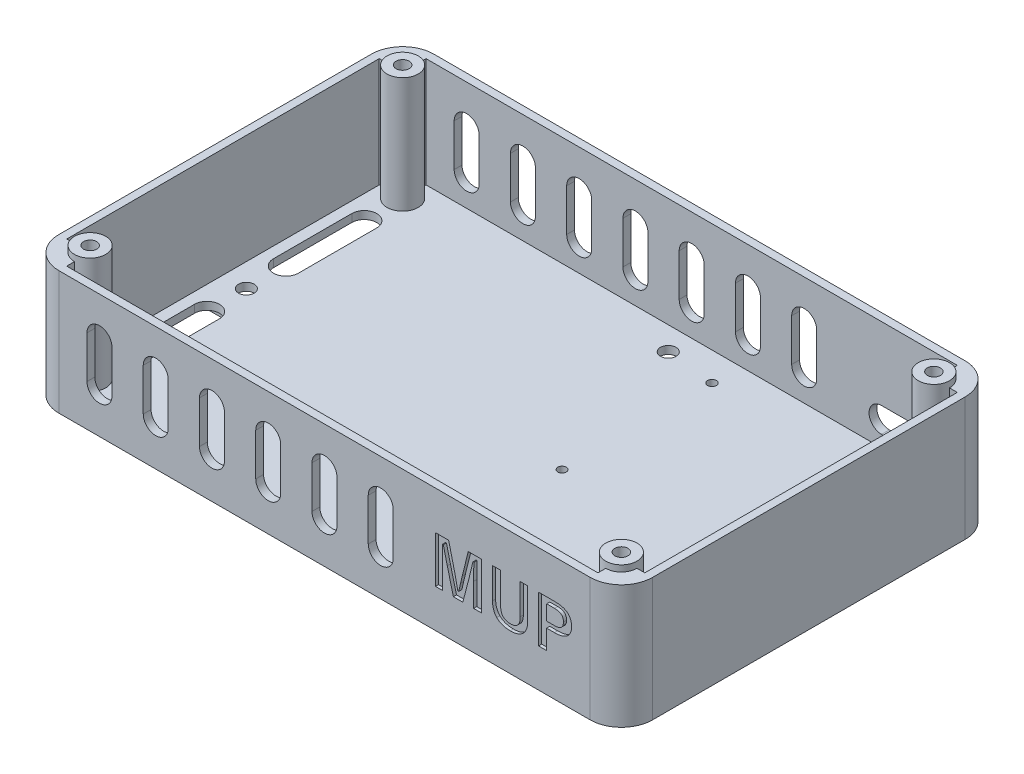
SolidWorks part; units mm, degrees
ref_plane "Front Plane" through (0, 0, 0) normal (0, 0, 1) x (1, 0, 0)
ref_plane "Top Plane" through (0, 0, 0) normal (0, 1, 0) x (1, 0, 0)
ref_plane "Right Plane" through (0, 0, 0) normal (1, 0, 0) x (0, 0, -1)
sketch "Sketch1" plane through (0, 94.5, 0) normal (0, 1, 0) x (1, 0, 0)
  line L0 (7.3241, -194.8914) -> (7.3241, -202.3914)
  line L1 (-7.6759, -194.8914) -> (-7.6759, -202.3914)
  line L2 (-85.1759, -152.3914) -> (-92.6759, -152.3914)
  line L3 (-84.9375, -137.4848) -> (-92.6759, -137.4848)
  line L4 (7.3241, -94.8914) -> (7.3241, -87.3914)
  line L5 (-7.6415, -94.1735) -> (-7.6759, -94.1891)
  line L7 (-7.6759, -94.8914) -> (-7.6759, -87.3914)
  line L9 (84.8241, -152.3914) -> (92.3241, -152.3914)
  line L10 (84.8241, -137.3914) -> (92.3241, -137.3914)
  line L16 (84.8241, -87.3914) -> (4.8241, -87.3914)
  line L17 (4.8241, -87.3914) -> (4.8241, -94.8914)
  line L18 (-5.1759, -94.8914) -> (-5.1759, -87.3914)
  line L19 (-5.1759, -87.3914) -> (-85.1759, -87.3914)
  line L20 (-92.6759, -94.8914) -> (-92.6759, -139.8914)
  line L21 (-92.6759, -139.8914) -> (-85.1759, -139.8914)
  line L22 (-85.1759, -149.8914) -> (-92.6759, -149.8914)
  line L23 (-92.6759, -149.8914) -> (-92.6759, -194.8914)
  line L24 (-85.1759, -202.3914) -> (-5.1759, -202.3914)
  line L25 (-5.1759, -202.3914) -> (-5.1759, -194.8914)
  line L26 (4.8241, -194.8914) -> (4.8241, -202.3914)
  line L27 (4.8241, -202.3914) -> (84.8241, -202.3914)
  line L28 (92.3241, -194.8914) -> (92.3241, -149.8914)
  line L29 (92.3241, -149.8914) -> (84.8241, -149.8914)
  line L30 (84.8241, -139.8914) -> (92.3241, -139.8914)
  line L31 (92.3241, -139.8914) -> (92.3241, -94.8914)
  line L32 (84.8241, -87.3914) -> (7.3241, -87.3914)
  line L35 (-7.6759, -87.3914) -> (-85.1759, -87.3914)
  line L36 (-92.6759, -94.8914) -> (-92.6759, -137.4848)
  line L39 (-92.6759, -152.3914) -> (-92.6759, -194.8914)
  line L40 (-85.1759, -202.3914) -> (-7.6759, -202.3914)
  line L43 (7.3241, -202.3914) -> (84.8241, -202.3914)
  line L44 (92.3241, -194.8914) -> (92.3241, -152.3914)
  line L47 (92.3241, -137.3914) -> (92.3241, -94.8914)
  circle A0 centre (84.8241, -144.8914) radius 5.5
  circle A1 centre (-0.1759, -194.8914) radius 5.5
  circle A2 centre (-85.1759, -144.8914) radius 5.5
  circle A3 centre (-0.1759, -94.8914) radius 5.5
  circle A5 centre (-0.1759, -194.8914) radius 7.5
  circle A7 centre (-0.1759, -94.8914) radius 7.5
  arc A8 (92.3241, -94.8914) -> (84.8241, -87.3914) centre (84.8241, -94.8914) ccw
  arc A9 (-5.1759, -94.8914) -> (4.8241, -94.8914) centre (-0.1759, -94.8914) ccw
  arc A10 (-85.1759, -87.3914) -> (-92.6759, -94.8914) centre (-85.1759, -94.8914) ccw
  arc A11 (-85.1759, -149.8914) -> (-85.1759, -139.8914) centre (-85.1759, -144.8914) ccw
  arc A12 (-92.6759, -194.8914) -> (-85.1759, -202.3914) centre (-85.1759, -194.8914) ccw
  arc A13 (4.8241, -194.8914) -> (-5.1759, -194.8914) centre (-0.1759, -194.8914) ccw
  arc A14 (84.8241, -202.3914) -> (92.3241, -194.8914) centre (84.8241, -194.8914) ccw
  arc A15 (84.8241, -139.8914) -> (84.8241, -149.8914) centre (84.8241, -144.8914) ccw
  arc A16 (92.3241, -94.8914) -> (84.8241, -87.3914) centre (84.8241, -94.8914) ccw
  arc A18 (-85.1759, -87.3914) -> (-92.6759, -94.8914) centre (-85.1759, -94.8914) ccw
  arc A20 (-92.6759, -194.8914) -> (-85.1759, -202.3914) centre (-85.1759, -194.8914) ccw
  arc A22 (84.8241, -202.3914) -> (92.3241, -194.8914) centre (84.8241, -194.8914) ccw
  circle A24 centre (84.8241, -144.8914) radius 7.5
  circle A25 centre (-85.1759, -144.8914) radius 7.5
  arc A26 (-88.9375, -133.4848) -> (-80.9375, -133.4848) centre (-84.9375, -133.4848) ccw construction
  line M25 (84.8241, -84.8914) -> (-85.1759, -84.8914)
  arc M26 (-85.1759, -84.8914) -> (-95.1759, -94.8914) centre (-85.1759, -94.8914) ccw
  line M27 (-95.1759, -94.8914) -> (-95.1759, -194.8914)
  arc M28 (-95.1759, -194.8914) -> (-85.1759, -204.8914) centre (-85.1759, -194.8914) ccw
  line M29 (-85.1759, -204.8914) -> (84.8241, -204.8914)
  arc M30 (84.8241, -204.8914) -> (94.8241, -194.8914) centre (84.8241, -194.8914) ccw
  line M31 (94.8241, -194.8914) -> (94.8241, -94.8914)
  arc M32 (94.8241, -94.8914) -> (84.8241, -84.8914) centre (84.8241, -94.8914) ccw
  line M33 (4.8241, -202.3914) -> (4.8241, -194.8914)
  line M35 (-5.1759, -194.8914) -> (-5.1759, -202.3914)
  line M36 (-5.1759, -202.3914) -> (-85.1759, -202.3914)
  arc M37 (-85.1759, -202.3914) -> (-92.6759, -194.8914) centre (-85.1759, -194.8914) cw
  line M38 (-92.6759, -194.8914) -> (-92.6759, -149.8914)
  line M39 (-92.6759, -149.8914) -> (-85.1759, -149.8914)
  line M41 (-85.1759, -139.8914) -> (-92.6759, -139.8914)
  line M42 (-92.6759, -139.8914) -> (-92.6759, -94.8914)
  arc M43 (-92.6759, -94.8914) -> (-85.1759, -87.3914) centre (-85.1759, -94.8914) cw
  line M44 (-85.1759, -87.3914) -> (-5.1759, -87.3914)
  line M45 (-5.1759, -87.3914) -> (-5.1759, -94.8914)
  line M47 (4.8241, -94.8914) -> (4.8241, -87.3914)
  line M48 (4.8241, -87.3914) -> (84.8241, -87.3914)
  arc M49 (84.8241, -87.3914) -> (92.3241, -94.8914) centre (84.8241, -94.8914) cw
  line M50 (92.3241, -94.8914) -> (92.3241, -139.8914)
  line M51 (92.3241, -139.8914) -> (84.8241, -139.8914)
  line M53 (84.8241, -149.8914) -> (92.3241, -149.8914)
  line M54 (92.3241, -149.8914) -> (92.3241, -194.8914)
  arc M55 (92.3241, -194.8914) -> (84.8241, -202.3914) centre (84.8241, -194.8914) cw
  line M56 (84.8241, -202.3914) -> (4.8241, -202.3914)
  dimension "D2" = 11
  dimension "D1" = 0
extrude "Boss-Extrude1" add sketch "Sketch1" along normal blind 2 contours A25 A7 A24 A5 M32 M25 M26 M27 M28 M29 M30 M31 M41 M42 M43 M44 M45 M47 M48 M49 M50 M51 M53 M54 M55 M56 M33 M35 M36 M37 M38 M39 | A24 A0 M53 M51 | A24 A0 M53 M51 | A24 L9 M54 M53 | A24 L10 M51 M50 | A5 A1 M33 M35 | A5 A1 M35 M33 | A5 L0 M33 M56 | A5 L1 M36 M35 | A25 L2 M39 M38 | A25 L3 M42 M41 | A25 A2 M41 M39 | A25 A2 M41 M39 | A7 A3 M47 M45 | A7 A3 M47 M45 | A7 L4 M48 M47 | A7 L7 L5 M45 M44 region at (6.4889, 94.5, 197.872) region at (6.324, 94.5, 200.3464) region at (-6.6758, 94.5, 200.3464) region at (-0.1759, 94.5, 200.5378) region at (90.2791, 94.5, 151.3913) region at (77.5231, 94.5, 144.8914) region at (-90.631, 94.5, 151.3913) region at (90.2791, 94.5, 138.3915) region at (90.4705, 94.5, 144.8914) region at (-88.1565, 94.5, 151.5562) region at (-90.8224, 94.5, 144.8914) region at (-90.7288, 94.5, 138.4624) region at (6.324, 94.5, 89.4364) region at (-0.1759, 94.5, 102.1923) region at (-0.1759, 94.5, 89.245) region at (-6.675, 94.5, 89.432) region at (90.3061, 94.5, 89.4094)
sketch "Sketch2" plane through (0, 96.5, 0) normal (0, 1, 0) x (1, 0, 0)
  line L4 (84.8241, -84.8914) -> (-85.1759, -84.8914)
  line L5 (-95.1759, -94.8914) -> (-95.1759, -194.8914)
  line L6 (-85.1759, -204.8914) -> (84.8241, -204.8914)
  line L7 (94.8241, -194.8914) -> (94.8241, -94.8914)
  line L8 (84.8241, -84.8914) -> (-85.1759, -84.8914)
  line L9 (-95.1759, -94.8914) -> (-95.1759, -194.8914)
  line L10 (-85.1759, -204.8914) -> (84.8241, -204.8914)
  line L11 (94.8241, -194.8914) -> (94.8241, -94.8914)
  arc A4 (94.8241, -94.8914) -> (84.8241, -84.8914) centre (84.8241, -94.8914) ccw
  arc A5 (-85.1759, -84.8914) -> (-95.1759, -94.8914) centre (-85.1759, -94.8914) ccw
  arc A6 (-95.1759, -194.8914) -> (-85.1759, -204.8914) centre (-85.1759, -194.8914) ccw
  arc A7 (84.8241, -204.8914) -> (94.8241, -194.8914) centre (84.8241, -194.8914) ccw
  arc A8 (94.8241, -94.8914) -> (84.8241, -84.8914) centre (84.8241, -94.8914) ccw
  arc A9 (-85.1759, -84.8914) -> (-95.1759, -94.8914) centre (-85.1759, -94.8914) ccw
  arc A10 (-95.1759, -194.8914) -> (-85.1759, -204.8914) centre (-85.1759, -194.8914) ccw
  arc A11 (84.8241, -204.8914) -> (94.8241, -194.8914) centre (84.8241, -194.8914) ccw
  dimension "D1" = 0
extrude "Boss-Extrude2" add sketch "Sketch2" along normal blind 2.5
sketch "Sketch5" plane through (0, 99, 0) normal (0, 1, 0) x (1, 0, 0)
  line L4 (-95.1759, -144.8914) -> (108.7771, -144.8914) construction
  line L5 (-95.1759, -94.8914) -> (-95.1759, -194.8914) construction
  line L8 (-80.9375, -132.4549) -> (-80.9375, -107.3914)
  line L9 (-88.9375, -107.3914) -> (-88.9375, -132.4549)
  line L10 (-88.9375, -182.3914) -> (-88.9375, -157.3279)
  line L11 (-80.9375, -157.3279) -> (-80.9375, -182.3914)
  line L16 (-85.1759, -89.8914) -> (-85.1759, -87.3914)
  line L17 (-90.1759, -94.8914) -> (-92.6759, -94.8914)
  line L18 (-92.6759, -194.8914) -> (-90.1759, -194.8914)
  line L19 (-85.1759, -199.8914) -> (-85.1759, -202.3914)
  line L20 (84.8241, -87.3914) -> (-85.1759, -87.3914)
  line L21 (-92.6759, -94.8914) -> (-92.6759, -194.8914)
  line L22 (-85.1759, -202.3914) -> (84.8241, -202.3914)
  line L23 (92.3241, -194.8914) -> (92.3241, -94.8914)
  line L24 (84.8241, -87.3914) -> (-85.1759, -87.3914)
  line L25 (-92.6759, -94.8914) -> (-92.6759, -194.8914)
  line L26 (-85.1759, -202.3914) -> (84.8241, -202.3914)
  line L27 (92.3241, -194.8914) -> (92.3241, -94.8914)
  line L28 (84.8241, -87.3914) -> (84.8241, -89.8914)
  line L29 (92.3241, -94.8914) -> (89.8241, -94.8914)
  line L30 (84.8241, -199.8914) -> (84.8241, -202.3914)
  line L31 (92.3241, -194.8914) -> (89.8241, -194.8914)
  circle A0 centre (-85.1759, -94.8914) radius 5
  circle A1 centre (84.8241, -94.8914) radius 5
  circle A2 centre (84.8241, -194.8914) radius 5
  circle A3 centre (-85.1759, -194.8914) radius 5
  arc A8 (-88.9375, -157.3279) -> (-80.9375, -157.3279) centre (-84.9375, -157.3279) cw
  arc A9 (-80.9375, -182.3914) -> (-88.9375, -182.3914) centre (-84.9375, -182.3914) cw
  arc A12 (-88.9375, -132.4549) -> (-80.9375, -132.4549) centre (-84.9375, -132.4549) ccw
  arc A13 (-80.9375, -107.3914) -> (-88.9375, -107.3914) centre (-84.9375, -107.3914) ccw
  arc A22 (92.3241, -94.8914) -> (84.8241, -87.3914) centre (84.8241, -94.8914) ccw
  arc A23 (-85.1759, -87.3914) -> (-92.6759, -94.8914) centre (-85.1759, -94.8914) ccw
  arc A24 (-92.6759, -194.8914) -> (-85.1759, -202.3914) centre (-85.1759, -194.8914) ccw
  arc A25 (84.8241, -202.3914) -> (92.3241, -194.8914) centre (84.8241, -194.8914) ccw
  arc A26 (92.3241, -94.8914) -> (84.8241, -87.3914) centre (84.8241, -94.8914) ccw
  arc A27 (-85.1759, -87.3914) -> (-92.6759, -94.8914) centre (-85.1759, -94.8914) ccw
  arc A28 (-92.6759, -194.8914) -> (-85.1759, -202.3914) centre (-85.1759, -194.8914) ccw
  arc A29 (84.8241, -202.3914) -> (92.3241, -194.8914) centre (84.8241, -194.8914) ccw
  point P14 (-84.9375, -103.3914)
  arc M14 (94.8241, -94.8914) -> (84.8241, -84.8914) centre (84.8241, -94.8914) ccw
  line M15 (84.8241, -84.8914) -> (-85.1759, -84.8914)
  arc M16 (-85.1759, -84.8914) -> (-95.1759, -94.8914) centre (-85.1759, -94.8914) ccw
  line M17 (-95.1759, -94.8914) -> (-95.1759, -194.8914)
  arc M18 (-95.1759, -194.8914) -> (-85.1759, -204.8914) centre (-85.1759, -194.8914) ccw
  line M19 (-85.1759, -204.8914) -> (84.8241, -204.8914)
  arc M20 (84.8241, -204.8914) -> (94.8241, -194.8914) centre (84.8241, -194.8914) ccw
  line M21 (94.8241, -194.8914) -> (94.8241, -94.8914)
  dimension "D1" = 18.5
  dimension "D2" = 2.5
extrude "Boss-Extrude4" add sketch "Sketch5" along normal blind 35 contours L4 L25 A27 L24 A26 L27 M17 M21 M14 M15 M16 | L4 L27 A29 L26 A28 L25 M17 M18 M19 M20 M21 | L16 A27 L17 A0 | A0 | A3 | L18 A28 L19 A3 | A2 | L30 A29 L31 A2 | A1 | L29 A26 L28 A1 region at (-93.1835, 99, 119.8914) region at (-93.9259, 99, 146.8839) region at (-89.2079, 99, 90.8595) region at (-89.2079, 99, 198.9233) region at (88.856, 99, 198.9233) region at (88.856, 99, 90.8595) region at (-85.1759, 99, 94.8914) region at (-85.1759, 99, 194.8914) region at (84.8241, 99, 194.8914) region at (84.8241, 99, 94.8914)
hole_wizard "Ø5.0 (5) Diameter Hole1" positions "Sketch6" profile "Sketch7" hole size "Ø5.0" standard "ISO"
sketch "Sketch6" plane through (0, 99, 0) normal (0, 1, 0) x (1, 0, 0)
  point P0 (-0.1759, -94.8914)
  point P3 (-85.1759, -144.8914)
  point P6 (84.8241, -144.8914)
  point P9 (-0.1759, -194.8914)
sketch "Sketch7" plane through (-0.1759, 99, 94.8914) normal (1, 0, 0) x (0, 0, 1)
  line L0 (0, 0) -> (0, 4.0022)
  line L1 (0, 4.0022) -> (2.5, 2.5)
  line L2 (2.5, 2.5) -> (2.5, 0)
  line L5 (2.5, 0) -> (0, 0)
  line L10 (0, 4.0022) -> (-2.5, 2.5) construction
  line L11 (0, -6.35) -> (0, 107.95) construction
  dimension "Hole Dia." = 5
  dimension "Hole Depth" = 2.5
  dimension "Drill Angle" = 118
sketch "Sketch8" plane through (0, 134, 0) normal (0, 1, 0) x (1, 0, 0)
  circle A0 centre (-85.1759, -194.8914) radius 5
  circle A1 centre (-85.1759, -94.8914) radius 5
  circle A2 centre (84.8241, -94.8914) radius 5
  circle A3 centre (84.8241, -194.8914) radius 5
extrude "Boss-Extrude5" add sketch "Sketch8" along normal blind 2
hole_wizard "Tap Drill for M5 Tap1" positions "Sketch9" profile "Sketch10" hole size "M5" standard "ISO"
sketch "Sketch9" plane through (0, 136, 0) normal (0, 1, 0) x (1, 0, 0)
  point P0 (-85.1759, -94.8914)
  point P3 (-85.1759, -194.8914)
  point P6 (84.8241, -94.8914)
  point P9 (84.8241, -194.8914)
sketch "Sketch10" plane through (-85.1759, 136, 94.8914) normal (1, 0, 0) x (0, 0, 1)
  line L0 (0, 0) -> (0, 21.2618)
  line L1 (0, 21.2618) -> (2.1, 20)
  line L2 (2.1, 20) -> (2.1, 0)
  line L5 (2.1, 0) -> (0, 0)
  line L10 (0, 21.2618) -> (-2.1, 20) construction
  line L11 (0, -6.35) -> (0, 107.95) construction
  dimension "Hole Dia." = 4.2
  dimension "Hole Depth" = 20
  dimension "Drill Angle" = 118
sketch "Sketch11" plane through (0, 99, 0) normal (0, 1, 0) x (1, 0, 0)
  line L2 (-92.6759, -144.8914) -> (-43.1546, -144.8914) construction
  line L3 (-92.6759, -94.8914) -> (-92.6759, -194.8914) construction
  line L6 (-81.1408, -132.2653) -> (-81.1408, -107.2017)
  line L7 (-89.1408, -107.2017) -> (-89.1408, -132.2653)
  line L8 (-89.1408, -182.5811) -> (-89.1408, -157.5175)
  line L9 (-81.1408, -157.5175) -> (-81.1408, -182.5811)
  arc A2 (-81.1408, -182.5811) -> (-89.1408, -182.5811) centre (-85.1408, -182.5811) cw
  arc A3 (-89.1408, -157.5175) -> (-81.1408, -157.5175) centre (-85.1408, -157.5175) cw
  arc A6 (-89.1408, -132.2653) -> (-81.1408, -132.2653) centre (-85.1408, -132.2653) ccw
  arc A7 (-81.1408, -107.2017) -> (-89.1408, -107.2017) centre (-85.1408, -107.2017) ccw
extrude "Cut-Extrude2" cut sketch "Sketch11" against normal blind 2.5
sketch "Sketch12" plane through (0, 99, 0) normal (0, 1, 0) x (1, 0, 0)
  circle A4 centre (19.3504, -155.4853) radius 1.1
  circle A5 centre (77.3504, -155.4853) radius 1.1
  circle A6 centre (77.3504, -113.9352) radius 1.1
  circle A7 centre (19.3504, -113.9352) radius 1.1
sketch "Sketch16" plane through (0, 99, 0) normal (0, 1, 0) x (1, 0, 0)
  line L0 (92.3241, -194.8914) -> (92.3241, -94.8914) construction
  line L1 (74.7241, -101.3914) -> (16.7241, -101.3914) construction
  line L2 (74.7241, -101.3914) -> (74.7241, -149.3914) construction
  line L3 (74.7241, -149.3914) -> (16.7241, -149.3914) construction
  line L4 (16.7241, -101.3914) -> (16.7241, -149.3914) construction
  line L5 (84.8241, -87.3914) -> (-85.1759, -87.3914) construction
  dimension "D1" = 48
  dimension "D2" = 58
  dimension "D3" = 17.6
  dimension "D4" = 14
sketch "Sketch17" plane through (0, 99, 0) normal (0, 1, 0) x (1, 0, 0)
  circle A0 centre (15.4697, -144.5267) radius 1.35
  circle A1 centre (15.4697, -96.5267) radius 1.4045
  circle A2 centre (73.4697, -144.5267) radius 1.35
  circle A3 centre (73.4697, -96.5267) radius 1.35
extrude "Cut-Extrude3" cut sketch "Sketch17" against normal blind 2.5
sketch "Sketch18" plane through (0, 0, 204.8914) normal (0, 0, 1) x (1, 0, 0)
  line L2 (-74.4259, 117.75) -> (-60.9259, 117.75)
  line L3 (-60.9259, 125.75) -> (-74.4259, 125.75)
  line L4 (-85.1759, 134) -> (84.8241, 134) construction
  line L5 (-33.9259, 125.75) -> (-47.4259, 125.75)
  line L6 (-47.4259, 117.75) -> (-33.9259, 117.75)
  line L7 (-6.9259, 125.75) -> (-20.4259, 125.75)
  line L8 (-20.4259, 117.75) -> (-6.9259, 117.75)
  line L9 (20.0741, 125.75) -> (6.5741, 125.75)
  line L10 (6.5741, 117.75) -> (20.0741, 117.75)
  line L15 (-33.9259, 110.75) -> (-47.4259, 110.75)
  line L16 (-47.4259, 102.75) -> (-33.9259, 102.75)
  line L17 (-6.9259, 110.75) -> (-20.4259, 110.75)
  line L18 (-20.4259, 102.75) -> (-6.9259, 102.75)
  line L19 (20.0741, 110.75) -> (6.5741, 110.75)
  line L20 (6.5741, 102.75) -> (20.0741, 102.75)
  line L25 (-60.9259, 110.75) -> (-74.4259, 110.75)
  line L26 (-74.4259, 102.75) -> (-60.9259, 102.75)
  line L27 (-60.9259, 125.75) -> (-33.9259, 125.75) construction
  line L28 (-60.9259, 125.75) -> (-60.9259, 110.75) construction
  line L30 (47.0741, 125.75) -> (33.5741, 125.75) [skipped]
  line L31 (33.5741, 117.75) -> (47.0741, 117.75) [skipped]
  line L32 (74.0741, 125.75) -> (60.5741, 125.75) [skipped]
  line L33 (60.5741, 117.75) -> (74.0741, 117.75) [skipped]
  line L34 (47.0741, 110.75) -> (33.5741, 110.75) [skipped]
  line L35 (33.5741, 102.75) -> (47.0741, 102.75) [skipped]
  line L36 (74.0741, 110.75) -> (60.5741, 110.75) [skipped]
  line L37 (60.5741, 102.75) -> (74.0741, 102.75) [skipped]
  arc A2 (-60.9259, 117.75) -> (-60.9259, 125.75) centre (-60.9259, 121.75) ccw
  arc A3 (-74.4259, 125.75) -> (-74.4259, 117.75) centre (-74.4259, 121.75) ccw
  arc A4 (-33.9259, 117.75) -> (-33.9259, 125.75) centre (-33.9259, 121.75) ccw
  arc A5 (-47.4259, 125.75) -> (-47.4259, 117.75) centre (-47.4259, 121.75) ccw
  arc A6 (-6.9259, 117.75) -> (-6.9259, 125.75) centre (-6.9259, 121.75) ccw
  arc A7 (-20.4259, 125.75) -> (-20.4259, 117.75) centre (-20.4259, 121.75) ccw
  arc A8 (20.0741, 117.75) -> (20.0741, 125.75) centre (20.0741, 121.75) ccw
  arc A9 (6.5741, 125.75) -> (6.5741, 117.75) centre (6.5741, 121.75) ccw
  arc A14 (-33.9259, 102.75) -> (-33.9259, 110.75) centre (-33.9259, 106.75) ccw
  arc A15 (-47.4259, 110.75) -> (-47.4259, 102.75) centre (-47.4259, 106.75) ccw
  arc A16 (-6.9259, 102.75) -> (-6.9259, 110.75) centre (-6.9259, 106.75) ccw
  arc A17 (-20.4259, 110.75) -> (-20.4259, 102.75) centre (-20.4259, 106.75) ccw
  arc A18 (20.0741, 102.75) -> (20.0741, 110.75) centre (20.0741, 106.75) ccw
  arc A19 (6.5741, 110.75) -> (6.5741, 102.75) centre (6.5741, 106.75) ccw
  arc A24 (-60.9259, 102.75) -> (-60.9259, 110.75) centre (-60.9259, 106.75) ccw
  arc A25 (-74.4259, 110.75) -> (-74.4259, 102.75) centre (-74.4259, 106.75) ccw
  arc A26 (47.0741, 117.75) -> (47.0741, 125.75) centre (47.0741, 121.75) ccw [skipped]
  arc A27 (33.5741, 125.75) -> (33.5741, 117.75) centre (33.5741, 121.75) ccw [skipped]
  arc A28 (74.0741, 117.75) -> (74.0741, 125.75) centre (74.0741, 121.75) ccw [skipped]
  arc A29 (60.5741, 125.75) -> (60.5741, 117.75) centre (60.5741, 121.75) ccw [skipped]
  arc A30 (47.0741, 102.75) -> (47.0741, 110.75) centre (47.0741, 106.75) ccw [skipped]
  arc A31 (33.5741, 110.75) -> (33.5741, 102.75) centre (33.5741, 106.75) ccw [skipped]
  arc A32 (74.0741, 102.75) -> (74.0741, 110.75) centre (74.0741, 106.75) ccw [skipped]
  arc A33 (60.5741, 110.75) -> (60.5741, 102.75) centre (60.5741, 106.75) ccw [skipped]
  dimension "D1" = 8.25
  dimension "D4" = 90
  dimension "D5" = 27
  dimension "D2" = 6
  dimension "D3" = 2
sketch "Sketch19" plane through (0, 0, 84.8914) normal (0, 0, -1) x (-1, 0, 0)
  line L24 (-74.0741, 110.75) -> (-60.5741, 110.75)
  line L25 (-60.5741, 102.75) -> (-74.0741, 102.75)
  arc A24 (-60.5741, 102.75) -> (-60.5741, 110.75) centre (-60.5741, 106.75) ccw
  arc A25 (-74.0741, 110.75) -> (-74.0741, 102.75) centre (-74.0741, 106.75) ccw
extrude "Cut-Extrude5" cut sketch "Sketch19" against normal blind 2.5
sketch "Sketch20" plane through (0, 0, 204.8914) normal (0, 0, 1) x (1, 0, 0)
  line L0 (33.5741, 106.75) -> (74.0741, 106.75) construction
  text T0 "MUP" font "Yu Gothic" height in points 48
extrude "Cut-Extrude6" cut sketch "Sketch20" against normal blind 1
sketch "Sketch21" plane through (0, 0, 204.8914) normal (0, 0, 1) x (1, 0, 0)
  line L0 (-72.1759, 121.26) -> (-72.1759, 107.76) construction
  line L1 (-68.1759, 121.26) -> (-68.1759, 107.76)
  line L2 (-76.1759, 121.26) -> (-76.1759, 107.76)
  line L3 (-85.1759, 134) -> (-85.1759, 94.5) construction
  line L4 (-58.1759, 121.26) -> (-58.1759, 107.76)
  line L5 (-50.1759, 121.26) -> (-50.1759, 107.76)
  line L6 (-54.1759, 121.26) -> (-54.1759, 107.76) construction
  line L7 (-40.1759, 121.26) -> (-40.1759, 107.76)
  line L8 (-32.1759, 121.26) -> (-32.1759, 107.76)
  line L9 (-36.1759, 121.26) -> (-36.1759, 107.76) construction
  line L10 (-22.1759, 121.26) -> (-22.1759, 107.76)
  line L11 (-14.1759, 121.26) -> (-14.1759, 107.76)
  line L12 (-18.1759, 121.26) -> (-18.1759, 107.76) construction
  line L13 (-4.1759, 121.26) -> (-4.1759, 107.76)
  line L14 (3.8241, 121.26) -> (3.8241, 107.76)
  line L15 (-0.1759, 121.26) -> (-0.1759, 107.76) construction
  line L16 (13.8241, 121.26) -> (13.8241, 107.76)
  line L17 (21.8241, 121.26) -> (21.8241, 107.76)
  line L18 (17.8241, 121.26) -> (17.8241, 107.76) construction
  arc A0 (-68.1759, 121.26) -> (-76.1759, 121.26) centre (-72.1759, 121.26) ccw
  arc A1 (-76.1759, 107.76) -> (-68.1759, 107.76) centre (-72.1759, 107.76) ccw
  arc A2 (-50.1759, 121.26) -> (-58.1759, 121.26) centre (-54.1759, 121.26) ccw
  arc A3 (-58.1759, 107.76) -> (-50.1759, 107.76) centre (-54.1759, 107.76) ccw
  arc A4 (-32.1759, 121.26) -> (-40.1759, 121.26) centre (-36.1759, 121.26) ccw
  arc A5 (-40.1759, 107.76) -> (-32.1759, 107.76) centre (-36.1759, 107.76) ccw
  arc A6 (-14.1759, 121.26) -> (-22.1759, 121.26) centre (-18.1759, 121.26) ccw
  arc A7 (-22.1759, 107.76) -> (-14.1759, 107.76) centre (-18.1759, 107.76) ccw
  arc A8 (3.8241, 121.26) -> (-4.1759, 121.26) centre (-0.1759, 121.26) ccw
  arc A9 (-4.1759, 107.76) -> (3.8241, 107.76) centre (-0.1759, 107.76) ccw
  arc A10 (21.8241, 121.26) -> (13.8241, 121.26) centre (17.8241, 121.26) ccw
  arc A11 (13.8241, 107.76) -> (21.8241, 107.76) centre (17.8241, 107.76) ccw
  point P2 (-72.1759, 114.51)
  point P9 (-68.1759, 114.51)
  point P14 (-54.1759, 114.51)
  point P21 (-36.1759, 114.51)
  point P28 (-18.1759, 114.51)
  point P35 (-0.1759, 114.51)
  point P42 (17.8241, 114.51)
  dimension "D1" = 9
  dimension "D2" = 8
  dimension "D3" = 6
extrude "Cut-Extrude7" cut sketch "Sketch21" against normal blind 2.5
sketch "Sketch24" plane through (0, 0, 84.8914) normal (0, 0, -1) x (-1, 0, 0)
  line L0 (76.1759, 121.26) -> (76.1759, 107.76) construction
  line L1 (68.1759, 107.76) -> (68.1759, 121.26) construction
  line L2 (76.1759, 121.26) -> (76.1759, 107.76)
  line L3 (68.1759, 107.76) -> (68.1759, 121.26)
  line L14 (58.1759, 121.26) -> (58.1759, 107.76)
  line L15 (50.1759, 107.76) -> (50.1759, 121.26)
  line L16 (40.1759, 121.26) -> (40.1759, 107.76)
  line L17 (32.1759, 107.76) -> (32.1759, 121.26)
  line L18 (22.1759, 121.26) -> (22.1759, 107.76)
  line L19 (14.1759, 107.76) -> (14.1759, 121.26)
  line L20 (4.1759, 121.26) -> (4.1759, 107.76)
  line L21 (-3.8241, 107.76) -> (-3.8241, 121.26)
  line L22 (-13.8241, 121.26) -> (-13.8241, 107.76)
  line L23 (-21.8241, 107.76) -> (-21.8241, 121.26)
  line L24 (-31.8241, 121.26) -> (-31.8241, 107.76)
  line L25 (-39.8241, 107.76) -> (-39.8241, 121.26)
  line L26 (76.1759, 121.26) -> (58.1759, 121.26) construction
  arc A0 (68.1759, 107.76) -> (76.1759, 107.76) centre (72.1759, 107.76) ccw construction
  arc A1 (76.1759, 121.26) -> (68.1759, 121.26) centre (72.1759, 121.26) ccw construction
  arc A2 (68.1759, 107.76) -> (76.1759, 107.76) centre (72.1759, 107.76) ccw
  arc A3 (76.1759, 121.26) -> (68.1759, 121.26) centre (72.1759, 121.26) ccw
  arc A14 (50.1759, 107.76) -> (58.1759, 107.76) centre (54.1759, 107.76) ccw
  arc A15 (58.1759, 121.26) -> (50.1759, 121.26) centre (54.1759, 121.26) ccw
  arc A16 (32.1759, 107.76) -> (40.1759, 107.76) centre (36.1759, 107.76) ccw
  arc A17 (40.1759, 121.26) -> (32.1759, 121.26) centre (36.1759, 121.26) ccw
  arc A18 (14.1759, 107.76) -> (22.1759, 107.76) centre (18.1759, 107.76) ccw
  arc A19 (22.1759, 121.26) -> (14.1759, 121.26) centre (18.1759, 121.26) ccw
  arc A20 (-3.8241, 107.76) -> (4.1759, 107.76) centre (0.1759, 107.76) ccw
  arc A21 (4.1759, 121.26) -> (-3.8241, 121.26) centre (0.1759, 121.26) ccw
  arc A22 (-21.8241, 107.76) -> (-13.8241, 107.76) centre (-17.8241, 107.76) ccw
  arc A23 (-13.8241, 121.26) -> (-21.8241, 121.26) centre (-17.8241, 121.26) ccw
  arc A24 (-39.8241, 107.76) -> (-31.8241, 107.76) centre (-35.8241, 107.76) ccw
  arc A25 (-31.8241, 121.26) -> (-39.8241, 121.26) centre (-35.8241, 121.26) ccw
  dimension "D2" = 18
  dimension "D1" = 7
extrude "Cut-Extrude8" cut sketch "Sketch24" against normal blind 2.5
